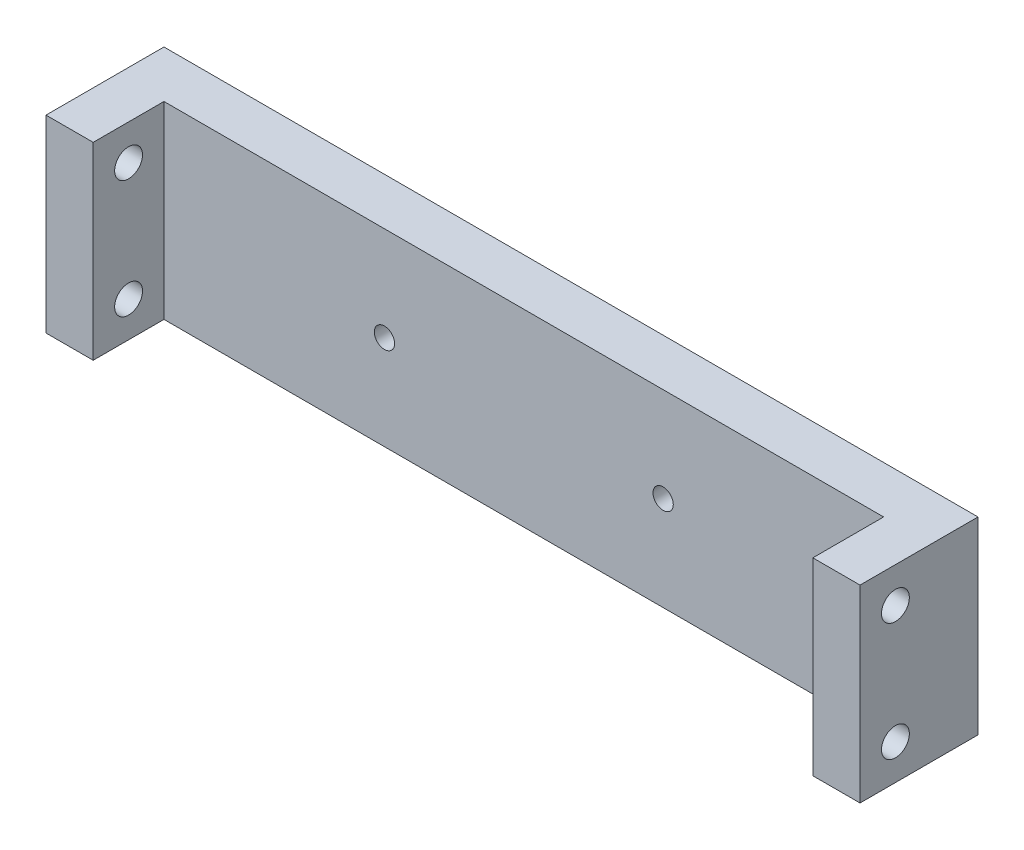
SolidWorks part; units mm, degrees
material "ABS"
ref_plane "Front Plane" through (0, 0, 0) normal (0, 0, 1) x (1, 0, 0)
ref_plane "Top Plane" through (0, 0, 0) normal (0, 1, 0) x (1, 0, 0)
ref_plane "Right Plane" through (0, 0, 0) normal (1, 0, 0) x (0, 0, -1)
sketch "Sketch1" plane through (0, 0, 0) normal (0, 0, 1) x (1, 0, 0)
  line L0 (82.55, 20.32) -> (82.55, 0)
  line L1 (0, 0) -> (87.63, 0)
  line L2 (0, 0) -> (0, 20.32)
  line L3 (0, 20.32) -> (87.63, 20.32)
  line L4 (87.63, 0) -> (87.63, 20.32)
  line L5 (5.08, 20.32) -> (5.08, 0)
  line L6 (5.08, 10.16) -> (82.55, 10.16) construction
  circle A0 centre (28.815, 10.16) radius 1.0922
  circle A1 centre (58.815, 10.16) radius 1.0922
  point P15 (43.815, 10.16)
  dimension "D3" = 30
  dimension "D6" = 2.1844
  dimension "D1" = 5.08
  dimension "D2" = 5.08
  dimension "D4" = 87.63
  dimension "D5" = 15
  dimension "D7" = 20.32
extrude "Boss-Extrude1" add sketch "Sketch1" along normal blind 5.08 contours L5 L6 A0 A1 L0 L3 | L6 L5 L1 L0 A1 A0 region at (43.815, 15.2621, 0) region at (43.815, 5.0579, 0)
extrude "Boss-Extrude2" add sketch "Sketch1<3>" along normal blind 12.7 contours L1 L4 L3 L0 | L5 L3 L2 L1 region at (85.09, 10.16, 0) region at (2.54, 10.16, 0)
sketch "Sketch1<3>" plane through (0, 0, 0) normal (0, 0, 1) x (1, 0, 0) same geometry as "Sketch1"
sketch "Sketch2" plane through (82.55, 0, 0) normal (-1, 0, 0) x (0, 0, 1)
  line L0 (8.89, 20.32) -> (8.89, 0) construction
  line L1 (12.7, 20.32) -> (5.08, 20.32) construction
  line L2 (12.7, 0) -> (5.08, 0) construction
  circle A0 centre (8.89, 16.51) radius 1.5
  circle A1 centre (8.89, 3.81) radius 1.5
  point P12 (8.89, 10.16)
  dimension "D1" = 12.7
  dimension "D2" = 6.35
  dimension "D3" = 3
extrude "Cut-Extrude1" cut sketch "Sketch2" along normal through all both and the other way through all
